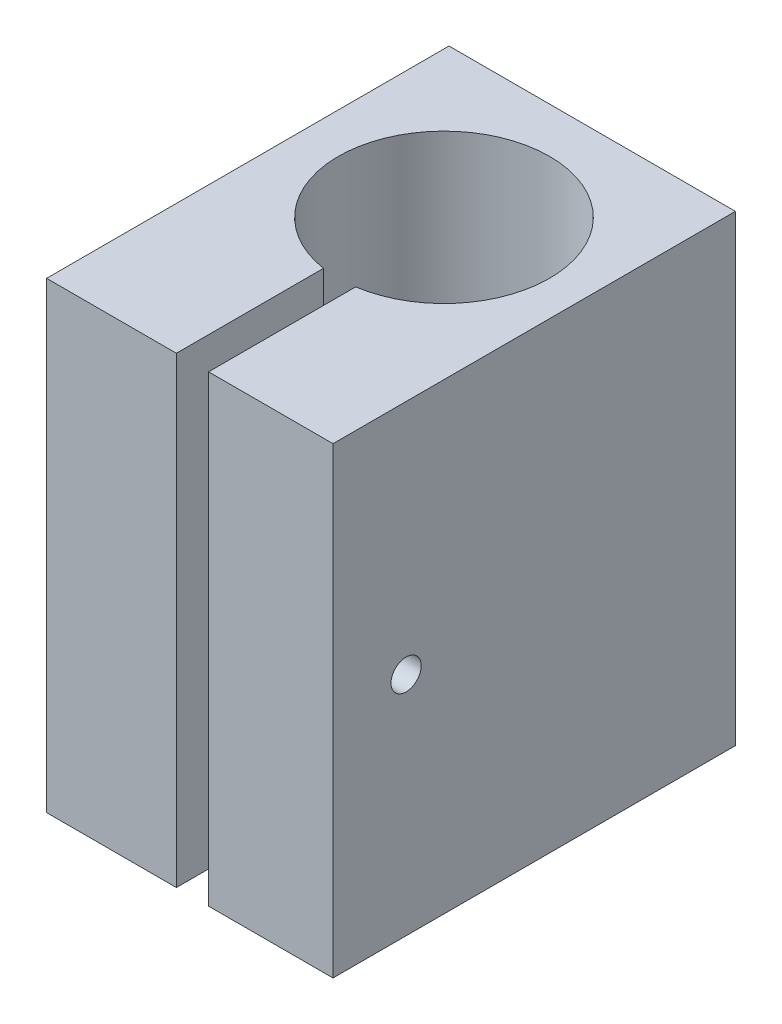
SolidWorks part; units mm, degrees
ref_plane "Спереди" through (0, 0, 0) normal (0, 0, 1) x (1, 0, 0)
ref_plane "Сверху" through (0, 0, 0) normal (0, 1, 0) x (1, 0, 0)
ref_plane "Справа" through (0, 0, 0) normal (1, 0, 0) x (0, 0, -1)
sketch "Эскиз1" plane through (0, 0, 0) normal (0, 1, 0) x (1, 0, 0)
  line L1 (-14.235, 20) -> (14.235, 20)
  line L2 (-14.235, 20) -> (-14.235, -20)
  line L3 (-14.235, -20) -> (-1.335, -20)
  line L4 (14.235, 20) -> (14.235, -20)
  line L5 (-14.235, 20) -> (14.235, -20) construction
  line L6 (-14.235, -20) -> (14.235, 20) construction
  line L7 (-39.5805, 5) -> (37.2286, 5) construction
  line L8 (-1.335, -20) -> (-1.335, -5.3774)
  line L9 (1.865, -20) -> (1.865, -5.3774)
  line L10 (1.865, -20) -> (14.235, -20)
  arc A0 (1.865, -5.3774) -> (-1.335, -5.3774) centre (0.265, 5) ccw
  point P0 (0, 0)
  dimension "D5" = 21
  dimension "D3" = 13.97
  dimension "D1" = 28.47
  dimension "D2" = 40
  dimension "D4" = 15
extrude "Бобышка-Вытянуть1" add sketch "Эскиз1" along normal blind 46
sketch "Эскиз2" plane through (-14.235, 0, 0) normal (-1, 0, 0) x (0, 0, 1)
  line L0 (12.733, 46) -> (12.733, 0) construction
  line L1 (-20, 46) -> (20, 46) construction
  line L2 (-20, 0) -> (20, 0) construction
  line L4 (15.7236, 21.1816) -> (15.8031, 24.6807)
  line L5 (15.8031, 24.6807) -> (12.8125, 26.4991)
  line L6 (12.8125, 26.4991) -> (9.7425, 24.8184)
  line L7 (9.7425, 24.8184) -> (9.6629, 21.3193)
  line L8 (9.6629, 21.3193) -> (12.6535, 19.5009)
  line L9 (12.6535, 19.5009) -> (15.7236, 21.1816)
  circle A0 centre (12.733, 23) radius 3.5 construction
  dimension "D1" = 7
extrude "Вырез-Вытянуть1" cut sketch "Эскиз2" against normal blind 3
sketch "Эскиз3" plane through (-11.235, 0, 0) normal (-1, 0, 0) x (0, 0, 1)
  circle A1 centre (12.733, 22.5) radius 1.5
  dimension "D1" = 3
extrude "Вырез-Вытянуть2" cut sketch "Эскиз3" against normal through all
